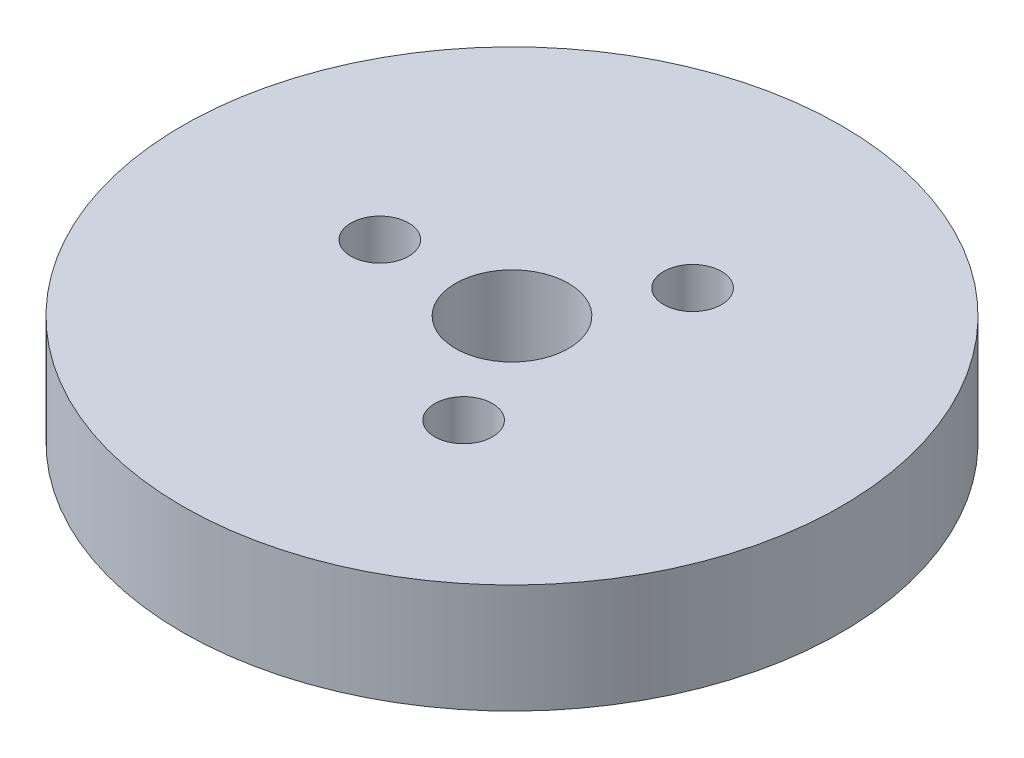
SolidWorks part; units mm, degrees
ref_plane "Front Plane" through (0, 0, 0) normal (0, 0, 1) x (1, 0, 0)
ref_plane "Top Plane" through (0, 0, 0) normal (0, 1, 0) x (1, 0, 0)
ref_plane "Right Plane" through (0, 0, 0) normal (1, 0, 0) x (0, 0, -1)
sketch "Sketch1" plane through (0, 0, 0) normal (0, 1, 0) x (1, 0, 0)
  circle A0 centre (0, 0) radius 87.5
  dimension "FLANGE_OD" = 175
extrude "Boss-Extrude1" add sketch "Sketch1" along normal blind 29
sketch "Sketch2" plane through (0, 0, 0) normal (0, 1, 0) x (1, 0, 0)
  circle A0 centre (0, 0) radius 15
  dimension "BORE_D" = 30
extrude "Cut-Extrude1" cut sketch "Sketch2" along normal through all
sketch "Sketch3" plane through (0, 29, 0) normal (0, 1, 0) x (1, 0, 0)
  circle A0 centre (0, 0) radius 35.0944 construction
  circle A1 centre (-35.0944, 0) radius 7.667
  dimension "BOLT_D" = 15.334
  dimension "BOLT_PCD" = 70.1888
extrude "Cut-Extrude2" cut sketch "Sketch3" against normal blind 21.2216
pattern_circular "CirPattern1" count 3 over 360 about axis through (0, 0, 0) along (0, 1, 0) of "Cut-Extrude2"
